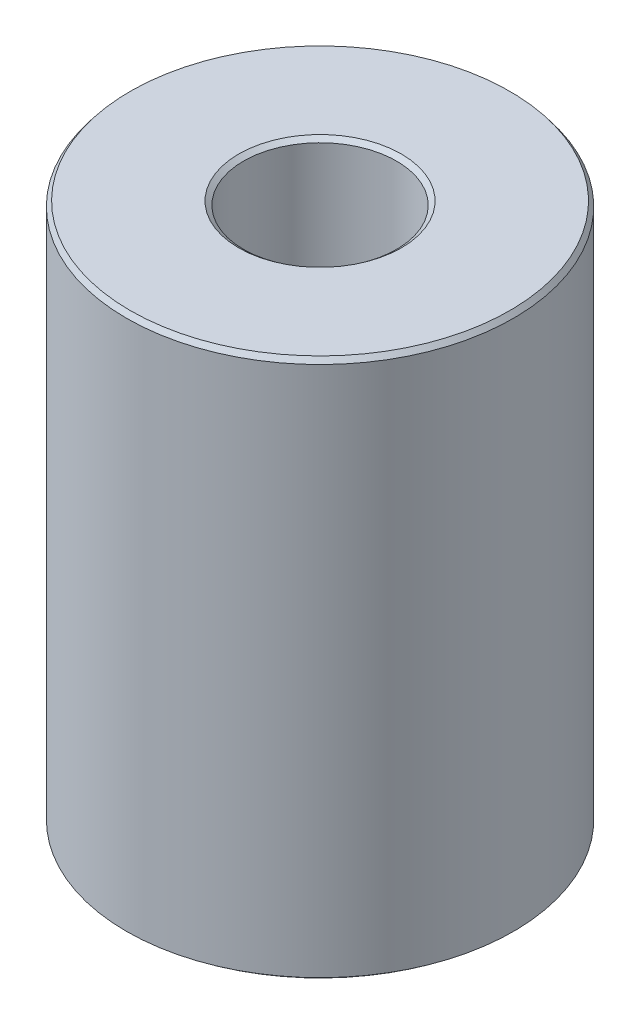
SolidWorks part; units mm, degrees
ref_plane "Front Plane" through (0, 0, 0) normal (0, 0, 1) x (1, 0, 0)
ref_plane "Top Plane" through (0, 0, 0) normal (0, 1, 0) x (1, 0, 0)
ref_plane "Right Plane" through (0, 0, 0) normal (1, 0, 0) x (0, 0, -1)
sketch "Sketch1" plane through (0, 0, 0) normal (0, 1, 0) x (1, 0, 0)
  circle A0 centre (0, 0) radius 47.5
  dimension "SLEEVE_OD" = 95
extrude "Boss-Extrude1" add sketch "Sketch1" along normal blind 132.4214
sketch "Sketch2" plane through (0, 0, 0) normal (0, 1, 0) x (1, 0, 0)
  circle A0 centre (0, 0) radius 18.7806
  dimension "BORE_D" = 37.5611
extrude "Cut-Extrude1" cut sketch "Sketch2" along normal through all
chamfer "Chamfer1" distance 1.1867 angle 37.366 4 edges at (0, 132.4214, 18.7806) (0, 0, 18.7806) (0, 0, 47.5) (0, 132.4214, 47.5) first distance on face at (0, 132.4214, 18.7806) first distance on face at (0, 0, 18.7806) first distance on face at (0, 132.4214, 47.5)
